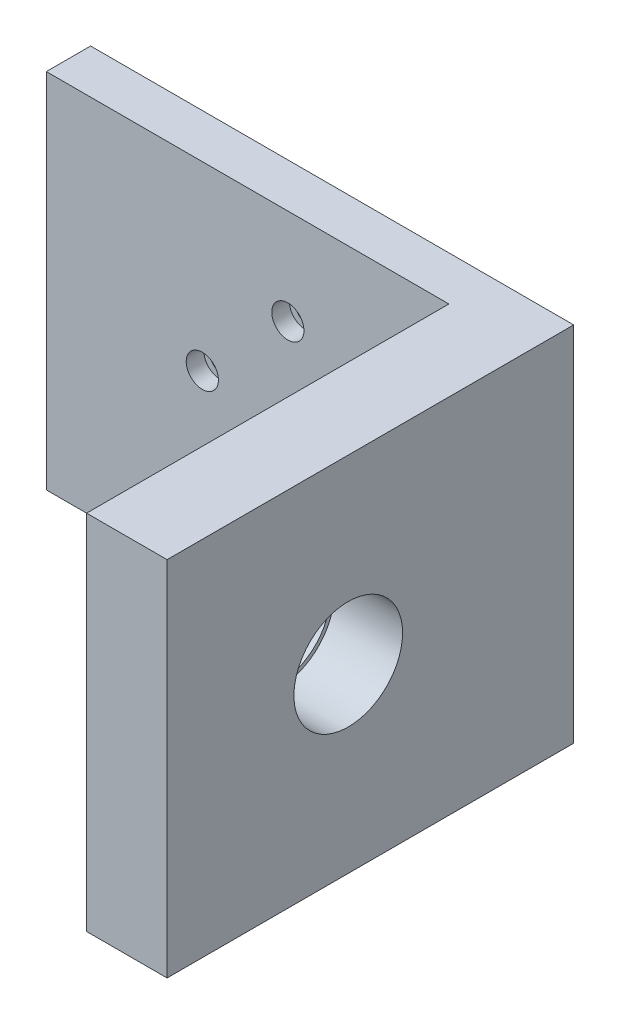
SolidWorks part; units mm, degrees
ref_plane "Front Plane" through (0, 0, 0) normal (0, 0, 1) x (1, 0, 0)
ref_plane "Top Plane" through (0, 0, 0) normal (0, 1, 0) x (1, 0, 0)
ref_plane "Right Plane" through (0, 0, 0) normal (1, 0, 0) x (0, 0, -1)
sketch "Sketch1" plane through (0, 0, 0) normal (0, 0, 1) x (1, 0, 0)
  line L1 (-60, -45) -> (60, -45)
  line L2 (-60, -45) -> (-60, 45)
  line L3 (-60, 45) -> (60, 45)
  line L4 (60, -45) -> (60, 45)
  line L5 (-60, -45) -> (60, 45) construction
  line L6 (-60, 45) -> (60, -45) construction
  circle A0 centre (0, 0) radius 41.25
  dimension "D1" = 82.5
  dimension "D2" = 90
  dimension "D3" = 120
extrude "Boss-Extrude1" add sketch "Sketch1" along normal blind 3
sketch "Sketch2" plane through (0, 0, 3) normal (0, 0, 1) x (1, 0, 0)
  line L4 (60, -45) -> (60, 45)
  line L5 (60, 45) -> (-60, 45)
  line L6 (-60, 45) -> (-60, -45)
  line L7 (-60, -45) -> (60, -45)
  line L8 (60, -45) -> (60, 45)
  line L9 (60, 45) -> (-60, 45)
  line L10 (-60, 45) -> (-60, -45)
  line L11 (-60, -45) -> (60, -45)
  dimension "D1" = 0
extrude "Boss-Extrude2" add sketch "Sketch2" along normal blind 8
hole_wizard "CBORE for M4 Hex Socket Head Cap Screw1" positions "Sketch3" profile "Sketch4" counterbore size "M4" standard "DIN" end condition through all
sketch "Sketch3" plane through (0, 0, 11) normal (0, 0, 1) x (1, 0, 0)
  circle A0 centre (0, 0) radius 21.25 construction
  point P5 (0, 21.25)
  point P11 (21.25, 0)
  point P12 (0, -21.25)
  point P13 (-21.25, 0)
  dimension "D1" = 42.5
  dimension "D2" = 4
sketch "Sketch4" plane through (-21.25, 0, 11) normal (1, 0, 0) x (0, -1, 0)
  line L0 (0, 0) -> (0, 11)
  line L1 (0, 11) -> (2.4, 11)
  line L3 (2.4, 11) -> (2.4, 4.4)
  line L4 (2.4, 4.4) -> (4, 4.4)
  line L5 (4, 4.4) -> (4, 0)
  line L7 (4, 0) -> (0, 0)
  line L11 (0, -6.35) -> (0, 107.95) construction
  dimension "Thru Hole Dia." = 4.8
  dimension "Thru Hole Depth" = 11
  dimension "C'Bore Dia." = 8
  dimension "C'Bore Depth" = 4.4
sketch "Sketch5" plane through (0, 0, 11) normal (0, 0, 1) x (1, 0, 0)
  line L0 (-60, -45) -> (60, -45) construction
  line L1 (60, 45) -> (40, 45)
  line L2 (60, 45) -> (60, -45)
  line L3 (60, -45) -> (40, -45)
  line L4 (40, 45) -> (40, -45)
  dimension "D1" = 20
extrude "Boss-Extrude3" add sketch "Sketch5" along normal blind 90
sketch "Sketch6" plane through (60, 0, 0) normal (1, 0, 0) x (0, 0, -1)
  line L0 (-101, 45) -> (-11, -45) construction
  line L1 (-11, 45) -> (-101, -45) construction
  line L4 (-11, -45) -> (-11, 45)
  line L5 (-101, -45) -> (-11, -45)
  line L6 (-101, 45) -> (-101, -45)
  line L7 (-11, 45) -> (-101, 45)
  line L8 (-11, -45) -> (-11, 45) construction
  line L9 (-101, -45) -> (-11, -45) construction
  line L10 (-101, 45) -> (-101, -45) construction
  line L11 (-11, 45) -> (-101, 45) construction
  circle A0 centre (-56, 0) radius 13.5
  dimension "D2" = 27
  dimension "D1" = 0
extrude "Cut-Extrude1" cut sketch "Sketch6" against normal blind 17
sketch "Sketch7" plane through (43, 0, 0) normal (1, 0, 0) x (0, 0, -1)
  circle A0 centre (-56, 0) radius 12.5
  circle A1 centre (-56, 0) radius 13.5 construction
  dimension "D1" = 25
extrude "Cut-Extrude2" cut sketch "Sketch7" against normal through all
